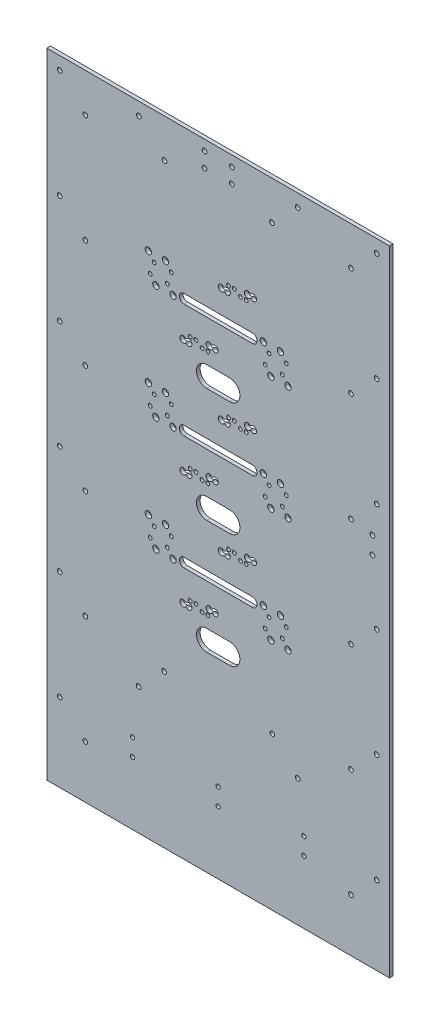
SolidWorks part; units mm, degrees
ref_plane "Front Plane" through (0, 0, 0) normal (0, 0, 1) x (1, 0, 0)
ref_plane "Top Plane" through (0, 0, 0) normal (0, 1, 0) x (1, 0, 0)
ref_plane "Right Plane" through (0, 0, 0) normal (1, 0, 0) x (0, 0, -1)
sketch "Sketch1" plane through (0, 0, 0) normal (0, 0, 1) x (1, 0, 0)
  line L0 (-165.9868, 389.7156) -> (134.0132, 389.7156) construction
  line L1 (-165.9868, 389.7156) -> (134.0132, 389.7156)
  line L2 (-165.9868, 389.7156) -> (-165.9868, -165.2844)
  line L3 (-165.9868, -165.2844) -> (134.0132, -165.2844)
  line L4 (134.0132, 389.7156) -> (134.0132, -165.2844)
  line L5 (89.0132, -165.2844) -> (134.0132, -165.2844) construction
  line L6 (134.0132, 389.7156) -> (134.0132, -165.2844) construction
  dimension "D2" = 300
extrude "Boss-Extrude1" add sketch "Sketch1" along normal blind 3.175
sketch "Sketch2" plane through (0, 0, 0) normal (0, 0, -1) x (-1, 0, 0)
  line L0 (15.9868, -165.2844) -> (15.9868, 389.7156) construction
  line L1 (165.9868, -165.2844) -> (-134.0132, -165.2844) construction
  line L2 (-134.0132, 389.7156) -> (165.9868, 389.7156) construction
  line L3 (0.9868, 59.7156) -> (30.9868, 59.7156) construction
  line L4 (0.9868, 159.7156) -> (30.9868, 159.7156) construction
  line L5 (0.9868, 259.7156) -> (30.9868, 259.7156) construction
  point P8 (15.9868, 59.7156)
  point P11 (15.9868, 159.7156)
  dimension "D1" = 30
  dimension "D2" = 30
  dimension "D3" = 100
  dimension "D4" = 100
  dimension "D5" = 130
sketch "Sketch4" plane through (0, 0, 3.175) normal (0, 0, 1) x (1, 0, 0)
  line L0 (-45.9868, 259.7156) -> (14.0132, 259.7156) construction
  line L1 (-45.9868, 263.7156) -> (14.0132, 263.7156)
  line L2 (-45.9868, 255.7156) -> (14.0132, 255.7156)
  line L3 (-15.9868, -165.2844) -> (-15.9868, 389.7156) construction
  line L4 (-0.9868, 259.7156) -> (-30.9868, 259.7156) construction
  line L5 (-45.9868, 159.7156) -> (14.0132, 159.7156) construction
  line L6 (-45.9868, 163.7156) -> (14.0132, 163.7156)
  line L7 (-45.9868, 155.7156) -> (14.0132, 155.7156)
  line L8 (-45.9868, 59.7156) -> (14.0132, 59.7156) construction
  line L9 (-45.9868, 63.7156) -> (14.0132, 63.7156)
  line L10 (-45.9868, 55.7156) -> (14.0132, 55.7156)
  line L11 (-0.9868, 59.7156) -> (-30.9868, 59.7156) construction
  line L12 (-0.9868, 159.7156) -> (-30.9868, 159.7156) construction
  arc A0 (-45.9868, 263.7156) -> (-45.9868, 255.7156) centre (-45.9868, 259.7156) ccw
  arc A1 (14.0132, 255.7156) -> (14.0132, 263.7156) centre (14.0132, 259.7156) ccw
  arc A2 (-45.9868, 163.7156) -> (-45.9868, 155.7156) centre (-45.9868, 159.7156) ccw
  arc A3 (14.0132, 155.7156) -> (14.0132, 163.7156) centre (14.0132, 159.7156) ccw
  arc A4 (-45.9868, 63.7156) -> (-45.9868, 55.7156) centre (-45.9868, 59.7156) ccw
  arc A5 (14.0132, 55.7156) -> (14.0132, 63.7156) centre (14.0132, 59.7156) ccw
  point P2 (-15.9868, 259.7156)
  point P14 (-15.9868, 159.7156)
  point P21 (-15.9868, 59.7156)
  dimension "D1" = 15
  dimension "D2" = 8
  dimension "D3" = 15
  dimension "D4" = 8
  dimension "D5" = 15
  dimension "D6" = 8
extrude "Cut-Extrude1" cut sketch "Sketch4" against normal blind 10
sketch "Sketch5" plane through (0, 0, 0) normal (0, 0, -1) x (-1, 0, 0)
  line L0 (45.9868, 155.7156) -> (-14.0132, 155.7156) construction
sketch "Sketch6" plane through (0, 0, 0) normal (0, 0, -1) x (-1, 0, 0)
  circle A0 centre (3.9868, 380.7156) radius 2.05
  circle A1 centre (27.9868, 380.7156) radius 2.05
  circle A2 centre (27.9868, 367.7156) radius 2.05
  circle A3 centre (3.9868, 367.7156) radius 2.05
  dimension "D1" = 4.1
extrude "Cut-Extrude5" cut sketch "Sketch6" against normal blind 51
sketch "Sketch8" plane through (0, 0, 0) normal (0, 0, -1) x (-1, 0, 0)
  circle A0 centre (-119.0132, 162.9803) radius 2.1
  circle A1 centre (-119.0132, 147.9803) radius 2.1
  dimension "D1" = 4.2
extrude "Cut-Extrude7" cut sketch "Sketch8" against normal blind 67
sketch "Sketch9" plane through (0, 0, 0) normal (0, 0, -1) x (-1, 0, 0)
  line L0 (15.9868, 389.7156) -> (15.9868, 432.1874) construction
  line L1 (-134.0132, 389.7156) -> (165.9868, 389.7156) construction
  circle A0 centre (-122.7632, 378.4656) radius 2.05
  circle A1 centre (-100.2632, 355.9656) radius 2.05
  circle A2 centre (-53.5368, 378.4656) radius 2.05
  circle A3 centre (-31.0368, 355.9656) radius 2.05
  circle A4 centre (-122.7632, 283.4656) radius 2.05
  circle A5 centre (-100.2632, 260.9656) radius 2.05
  circle A6 centre (-122.7632, 188.4656) radius 2.05
  circle A7 centre (-100.2632, 165.9656) radius 2.05
  circle A8 centre (-122.7632, 93.4656) radius 2.05
  circle A9 centre (-100.2632, 70.9656) radius 2.05
  circle A10 centre (-122.7632, -1.5344) radius 2.05
  circle A11 centre (-100.2632, -24.0344) radius 2.05
  circle A12 centre (-122.7632, -96.5344) radius 2.05
  circle A13 centre (-100.2632, -119.0344) radius 2.05
  circle A14 centre (-122.7632, -191.5344) radius 2.05
  circle A15 centre (-100.2632, -214.0344) radius 2.05
  circle A16 centre (-53.6482, -54.0344) radius 2.05
  circle A17 centre (-31.371, -31.5344) radius 2.05
  circle A18 centre (63.3447, -31.5344) radius 2.05
  circle A19 centre (85.6219, -54.0344) radius 2.05
  circle A20 centre (132.2368, -214.0344) radius 2.05
  circle A21 centre (154.7368, -191.5344) radius 2.05
  circle A22 centre (132.2368, -119.0344) radius 2.05
  circle A23 centre (154.7368, -96.5344) radius 2.05
  circle A24 centre (132.2368, -24.0344) radius 2.05
  circle A25 centre (154.7368, -1.5344) radius 2.05
  circle A26 centre (132.2368, 70.9656) radius 2.05
  circle A27 centre (154.7368, 93.4656) radius 2.05
  circle A28 centre (132.2368, 165.9656) radius 2.05
  circle A29 centre (154.7368, 188.4656) radius 2.05
  circle A30 centre (132.2368, 260.9656) radius 2.05
  circle A31 centre (154.7368, 283.4656) radius 2.05
  circle A32 centre (63.0104, 355.9656) radius 2.05
  circle A33 centre (85.5104, 378.4656) radius 2.05
  circle A34 centre (132.2368, 355.9656) radius 2.05
  circle A35 centre (154.7368, 378.4656) radius 2.05
  dimension "D1" = 7
extrude "Cut-Extrude8" cut sketch "Sketch9" against normal blind 10
sketch "Sketch10" plane through (0, 0, 0) normal (0, 0, -1) x (-1, 0, 0)
  circle A0 centre (35.464, 33.6216) radius 1.651
  circle A1 centre (25.1051, 30.1602) radius 1.651
  arc A2 (43.5999, 30.6974) -> (43.5999, 26.4941) centre (41.7588, 28.5958) ccw
  arc A3 (20.6514, 37.2877) -> (20.6514, 33.0844) centre (18.8103, 35.186) ccw
  circle A4 centre (-30.1263, 38.9336) radius 2.794
  circle A5 centre (-23.5434, 61.8842) radius 2.794
  circle A6 centre (-25.1024, 45.23) radius 1.651
  circle A7 centre (-28.5672, 55.5878) radius 1.651
  circle A8 centre (-45.1263, 38.9336) radius 2.794
  circle A9 centre (-38.5434, 61.8842) radius 2.794
  circle A10 centre (-40.1024, 45.23) radius 1.651
  circle A11 centre (-43.5672, 55.5878) radius 1.651
  circle A12 centre (40.464, 33.6216) radius 1.651
  circle A13 centre (30.1051, 30.1602) radius 1.651
  arc A14 (44.9177, 26.4941) -> (44.9177, 30.6974) centre (46.7588, 28.5958) ccw
  arc A15 (21.9693, 33.0844) -> (21.9693, 37.2877) centre (23.8103, 35.186) ccw
  arc A16 (21.9693, 33.0844) -> (20.6514, 33.0844) centre (21.3103, 32.3322) ccw
  arc A17 (21.9693, 37.2877) -> (20.6514, 37.2877) centre (21.3103, 38.0399) cw
  arc A18 (44.9177, 26.4941) -> (43.5999, 26.4941) centre (44.2588, 25.7419) ccw
  arc A19 (44.9177, 30.6974) -> (43.5999, 30.6974) centre (44.2588, 31.4496) cw
  circle A40 centre (55.5171, 57.5469) radius 2.794
  circle A41 centre (70.5171, 57.5469) radius 2.794
  circle A42 centre (75.5409, 63.8433) radius 1.651
  circle A43 centre (60.5409, 63.8433) radius 1.651
  circle A44 centre (-3.4904, 85.8095) radius 1.651
  circle A45 centre (6.8686, 89.271) radius 1.651
  arc A46 (-11.6262, 88.7337) -> (-11.6262, 92.937) centre (-9.7851, 90.8353) ccw
  arc A47 (11.3223, 82.1435) -> (11.3223, 86.3468) centre (13.1633, 84.2451) ccw
  circle A48 centre (62.0999, 80.4975) radius 2.794
  circle A49 centre (57.0761, 74.2011) radius 1.651
  circle A50 centre (77.0999, 80.4975) radius 2.794
  circle A51 centre (72.0761, 74.2011) radius 1.651
  circle A52 centre (-8.4904, 85.8095) radius 1.651
  circle A53 centre (1.8686, 89.271) radius 1.651
  arc A54 (-12.9441, 92.937) -> (-12.9441, 88.7337) centre (-14.7851, 90.8353) ccw
  arc A55 (10.0044, 86.3468) -> (10.0044, 82.1435) centre (8.1633, 84.2451) ccw
  arc A56 (10.0044, 86.3468) -> (11.3223, 86.3468) centre (10.6633, 87.099) ccw
  arc A57 (10.0044, 82.1435) -> (11.3223, 82.1435) centre (10.6633, 81.3913) cw
  arc A58 (-12.9441, 92.937) -> (-11.6262, 92.937) centre (-12.2851, 93.6892) ccw
  arc A59 (-12.9441, 88.7337) -> (-11.6262, 88.7337) centre (-12.2851, 87.9815) cw
  circle A60 centre (63.0104, 355.9656) radius 2.05 construction
  circle A62 centre (35.464, 133.6216) radius 1.651
  circle A63 centre (25.1051, 130.1602) radius 1.651
  arc A64 (43.5999, 130.6974) -> (43.5999, 126.4941) centre (41.7588, 128.5958) ccw
  arc A65 (20.6514, 137.2877) -> (20.6514, 133.0844) centre (18.8103, 135.186) ccw
  circle A66 centre (-30.1263, 138.9336) radius 2.794
  circle A67 centre (-23.5434, 161.8842) radius 2.794
  circle A68 centre (-25.1024, 145.23) radius 1.651
  circle A69 centre (-28.5672, 155.5878) radius 1.651
  circle A70 centre (-45.1263, 138.9336) radius 2.794
  circle A71 centre (-38.5434, 161.8842) radius 2.794
  circle A72 centre (-40.1024, 145.23) radius 1.651
  circle A73 centre (-43.5672, 155.5878) radius 1.651
  circle A74 centre (40.464, 133.6216) radius 1.651
  circle A75 centre (30.1051, 130.1602) radius 1.651
  arc A76 (44.9177, 126.4941) -> (44.9177, 130.6974) centre (46.7588, 128.5958) ccw
  arc A77 (21.9693, 133.0844) -> (21.9693, 137.2877) centre (23.8103, 135.186) ccw
  arc A78 (21.9693, 133.0844) -> (20.6514, 133.0844) centre (21.3103, 132.3322) ccw
  arc A79 (21.9693, 137.2877) -> (20.6514, 137.2877) centre (21.3103, 138.0399) cw
  arc A80 (44.9177, 126.4941) -> (43.5999, 126.4941) centre (44.2588, 125.7419) ccw
  arc A81 (44.9177, 130.6974) -> (43.5999, 130.6974) centre (44.2588, 131.4496) cw
  circle A82 centre (55.5171, 157.5469) radius 2.794
  circle A83 centre (70.5171, 157.5469) radius 2.794
  circle A84 centre (75.5409, 163.8433) radius 1.651
  circle A85 centre (60.5409, 163.8433) radius 1.651
  circle A86 centre (-3.4904, 185.8095) radius 1.651
  circle A87 centre (6.8686, 189.271) radius 1.651
  arc A88 (-11.6262, 188.7337) -> (-11.6262, 192.937) centre (-9.7851, 190.8353) ccw
  arc A89 (11.3223, 182.1435) -> (11.3223, 186.3468) centre (13.1633, 184.2451) ccw
  circle A90 centre (62.0999, 180.4975) radius 2.794
  circle A91 centre (57.0761, 174.2011) radius 1.651
  circle A92 centre (77.0999, 180.4975) radius 2.794
  circle A93 centre (72.0761, 174.2011) radius 1.651
  circle A94 centre (-8.4904, 185.8095) radius 1.651
  circle A95 centre (1.8686, 189.271) radius 1.651
  arc A96 (-12.9441, 192.937) -> (-12.9441, 188.7337) centre (-14.7851, 190.8353) ccw
  arc A97 (10.0044, 186.3468) -> (10.0044, 182.1435) centre (8.1633, 184.2451) ccw
  arc A98 (10.0044, 186.3468) -> (11.3223, 186.3468) centre (10.6633, 187.099) ccw
  arc A99 (10.0044, 182.1435) -> (11.3223, 182.1435) centre (10.6633, 181.3913) cw
  arc A100 (-12.9441, 192.937) -> (-11.6262, 192.937) centre (-12.2851, 193.6892) ccw
  arc A101 (-12.9441, 188.7337) -> (-11.6262, 188.7337) centre (-12.2851, 187.9815) cw
  circle A102 centre (35.464, 233.6216) radius 1.651
  circle A103 centre (25.1051, 230.1602) radius 1.651
  arc A104 (43.5999, 230.6974) -> (43.5999, 226.4941) centre (41.7588, 228.5958) ccw
  arc A105 (20.6514, 237.2877) -> (20.6514, 233.0844) centre (18.8103, 235.186) ccw
  circle A106 centre (-30.1263, 238.9336) radius 2.794
  circle A107 centre (-23.5434, 261.8842) radius 2.794
  circle A108 centre (-25.1024, 245.23) radius 1.651
  circle A109 centre (-28.5672, 255.5878) radius 1.651
  circle A110 centre (-45.1263, 238.9336) radius 2.794
  circle A111 centre (-38.5434, 261.8842) radius 2.794
  circle A112 centre (-40.1024, 245.23) radius 1.651
  circle A113 centre (-43.5672, 255.5878) radius 1.651
  circle A114 centre (40.464, 233.6216) radius 1.651
  circle A115 centre (30.1051, 230.1602) radius 1.651
  arc A116 (44.9177, 226.4941) -> (44.9177, 230.6974) centre (46.7588, 228.5958) ccw
  arc A117 (21.9693, 233.0844) -> (21.9693, 237.2877) centre (23.8103, 235.186) ccw
  arc A118 (21.9693, 233.0844) -> (20.6514, 233.0844) centre (21.3103, 232.3322) ccw
  arc A119 (21.9693, 237.2877) -> (20.6514, 237.2877) centre (21.3103, 238.0399) cw
  arc A120 (44.9177, 226.4941) -> (43.5999, 226.4941) centre (44.2588, 225.7419) ccw
  arc A121 (44.9177, 230.6974) -> (43.5999, 230.6974) centre (44.2588, 231.4496) cw
  circle A122 centre (55.5171, 257.5469) radius 2.794
  circle A123 centre (70.5171, 257.5469) radius 2.794
  circle A124 centre (75.5409, 263.8433) radius 1.651
  circle A125 centre (60.5409, 263.8433) radius 1.651
  circle A126 centre (-3.4904, 285.8095) radius 1.651
  circle A127 centre (6.8686, 289.271) radius 1.651
  arc A128 (-11.6262, 288.7337) -> (-11.6262, 292.937) centre (-9.7851, 290.8353) ccw
  arc A129 (11.3223, 282.1435) -> (11.3223, 286.3468) centre (13.1633, 284.2451) ccw
  circle A130 centre (62.0999, 280.4975) radius 2.794
  circle A131 centre (57.0761, 274.2011) radius 1.651
  circle A132 centre (77.0999, 280.4975) radius 2.794
  circle A133 centre (72.0761, 274.2011) radius 1.651
  circle A134 centre (-8.4904, 285.8095) radius 1.651
  circle A135 centre (1.8686, 289.271) radius 1.651
  arc A136 (-12.9441, 292.937) -> (-12.9441, 288.7337) centre (-14.7851, 290.8353) ccw
  arc A137 (10.0044, 286.3468) -> (10.0044, 282.1435) centre (8.1633, 284.2451) ccw
  arc A138 (10.0044, 286.3468) -> (11.3223, 286.3468) centre (10.6633, 287.099) ccw
  arc A139 (10.0044, 282.1435) -> (11.3223, 282.1435) centre (10.6633, 281.3913) cw
  arc A140 (-12.9441, 292.937) -> (-11.6262, 292.937) centre (-12.2851, 293.6892) ccw
  arc A141 (-12.9441, 288.7337) -> (-11.6262, 288.7337) centre (-12.2851, 287.9815) cw
  dimension "D3" = 1
  dimension "D4" = 1
  dimension "D5" = 3
  dimension "D1" = 2
  dimension "D2" = 2
extrude "Cut-Extrude9" cut sketch "Sketch10" against normal blind 10
sketch "Sketch12" plane through (0, 0, 0) normal (0, 0, -1) x (-1, 0, 0)
  circle A0 centre (90.9868, -95.2078) radius 1.85
  circle A1 centre (90.9868, -110.2078) radius 1.85
  circle A2 centre (15.9868, -95.2078) radius 1.85
  circle A3 centre (15.9868, -110.2078) radius 1.85
  circle A4 centre (-59.0132, -95.2078) radius 1.85
  circle A5 centre (-59.0132, -110.2078) radius 1.85
  dimension "D1" = 3
extrude "Cut-Extrude10" cut sketch "Sketch12" against normal blind 10
sketch "Sketch13" plane through (0, 0, 3.175) normal (0, 0, 1) x (1, 0, 0)
  line L0 (-15.9868, 55.7156) -> (-15.9868, 10.7156) construction
  line L1 (-45.9868, 55.7156) -> (14.0132, 55.7156) construction
  line L2 (-25.9868, 10.7156) -> (-5.9868, 10.7156) construction
  line L3 (-25.9868, 19.7156) -> (-5.9868, 19.7156)
  line L4 (-25.9868, 1.7156) -> (-5.9868, 1.7156)
  line L5 (14.0132, 63.7156) -> (-45.9868, 63.7156) construction
  line L6 (14.0132, 163.7156) -> (-45.9868, 163.7156) construction
  line L7 (-25.9868, 110.7156) -> (-5.9868, 110.7156) construction
  line L8 (-25.9868, 119.7156) -> (-5.9868, 119.7156)
  line L9 (-25.9868, 101.7156) -> (-5.9868, 101.7156)
  line L10 (-25.9868, 210.7156) -> (-5.9868, 210.7156) construction
  line L11 (-25.9868, 219.7156) -> (-5.9868, 219.7156)
  line L12 (-25.9868, 201.7156) -> (-5.9868, 201.7156)
  arc A0 (-25.9868, 19.7156) -> (-25.9868, 1.7156) centre (-25.9868, 10.7156) ccw
  arc A1 (-5.9868, 1.7156) -> (-5.9868, 19.7156) centre (-5.9868, 10.7156) ccw
  arc A2 (-25.9868, 119.7156) -> (-25.9868, 101.7156) centre (-25.9868, 110.7156) ccw
  arc A3 (-5.9868, 101.7156) -> (-5.9868, 119.7156) centre (-5.9868, 110.7156) ccw
  arc A4 (-25.9868, 219.7156) -> (-25.9868, 201.7156) centre (-25.9868, 210.7156) ccw
  arc A5 (-5.9868, 201.7156) -> (-5.9868, 219.7156) centre (-5.9868, 210.7156) ccw
  point P6 (-15.9868, 10.7156)
  point P19 (-15.9868, 110.7156)
  point P26 (-15.9868, 210.7156)
  dimension "D1" = 18
  dimension "D2" = 45
  dimension "D3" = 20
  dimension "D4" = 100
  dimension "D6" = 100
  dimension "D5" = 3
extrude "Cut-Extrude11" cut sketch "Sketch13" against normal blind 29.1
